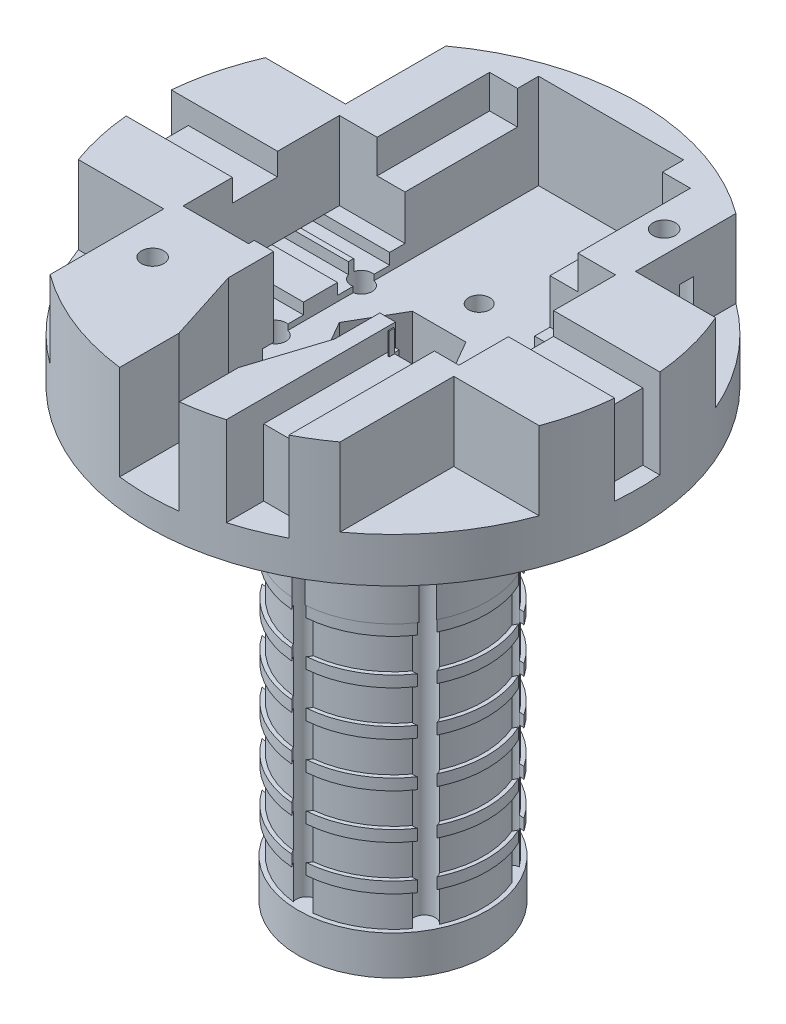
SolidWorks part; units mm, degrees
ref_plane "Front Plane" through (0, 0, 0) normal (0, 0, 1) x (1, 0, 0)
ref_plane "Top Plane" through (0, 0, 0) normal (0, 1, 0) x (1, 0, 0)
ref_plane "Right Plane" through (0, 0, 0) normal (1, 0, 0) x (0, 0, -1)
sketch "Sketch1" plane through (0, 0, 0) normal (0, 1, 0) x (1, 0, 0)
  circle A0 centre (0, 0) radius 22
extrude "Boss-Extrude1" add sketch "Sketch1" along normal blind 9 and the other way blind 2
sketch "Sketch2" plane through (0, 9, 0) normal (0, 1, 0) x (1, 0, 0)
  line L0 (0, 0) -> (0, -22) construction
  circle A0 centre (0, 0) radius 22 construction
ref_plane "Plane4" through (0, -2, 0) normal (0, -1, 0) x (-1, 0, 0)
sketch "Sketch6" plane through (0, -2, 0) normal (0, -1, 0) x (-1, 0, 0)
  circle A0 centre (0, 0) radius 21
  circle A1 centre (0, 0) radius 12.5
extrude "Cut-Extrude5" cut sketch "Sketch6" against normal blind 1
sketch "Sketch7" plane through (0, -2, 0) normal (0, -1, 0) x (-1, 0, 0)
  circle A0 centre (0, 0) radius 8.5
extrude "Boss-Extrude2" add sketch "Sketch7" along normal blind 40 contours A0
sketch "Sketch8" plane through (0, -2, 0) normal (0, -1, 0) x (-1, 0, 0)
  circle A0 centre (0, 0) radius 1.5
extrude "Cut-Extrude6" cut sketch "Sketch8" against normal through all and the other way through all contours A0
sketch "Sketch9" plane through (0, 9, 0) normal (0, 1, 0) x (1, 0, 0)
  line L0 (0, 0) -> (-13.0007, 0) construction
  line L1 (-13.0007, -20.3592) -> (-13.0007, 20.3592)
  line L2 (13, -20.3597) -> (13, 20.3597)
  line L3 (0, 0) -> (13, 0) construction
  arc A0 (13, -20.3597) -> (13, 20.3597) centre (0, 0) ccw
  arc A1 (-13.0007, 20.3592) -> (-13.0007, -20.3592) centre (0, 0) ccw
extrude "Cut-Extrude7" cut sketch "Sketch9" against normal blind 7
ref_plane "Plane5" through (0, -42, 0) normal (0, -1, 0) x (-1, 0, 0)
sketch "Sketch17" plane through (0, -42, 0) normal (0, -1, 0) x (-1, 0, 0)
  line L0 (-8.5, 0) -> (8.5, 0) construction
  line L2 (4.8118, -0.0068) -> (2.4118, 4.1501)
  line L3 (2.4118, 4.1501) -> (-2.3882, 4.1501)
  line L4 (-2.3882, 4.1501) -> (-4.7882, -0.0068)
  line L5 (-4.7882, -0.0068) -> (-2.3882, -4.1637)
  line L6 (-2.3882, -4.1637) -> (2.4118, -4.1637)
  line L7 (2.4118, -4.1637) -> (4.8118, -0.0068)
  line L38 (4.46, -2.575) -> (7.3614, -4.2497) construction
  line L39 (7.3614, -4.2497) -> (-7.3614, 4.2497) construction
  line L40 (0, 5.15) -> (0, -8.5) construction
  line L41 (0, -8.5) -> (0, 8.5) construction
  line L42 (-4.4482, -2.5818) -> (4.4718, 2.5682) construction
  line L43 (4.4718, 2.5682) -> (7.3671, 4.2398) construction
  line L44 (7.3671, 4.2398) -> (-7.3553, -4.2602) construction
  circle A0 centre (0, 0) radius 8.5 construction
  circle A1 centre (0, 0) radius 8.5 construction
  circle A2 centre (0.0118, -0.0068) radius 4.1569 construction
  circle A3 centre (-6.6912, 3.8628) radius 0.95
  circle A4 centre (-0.0004, 7.7262) radius 0.95
  circle A5 centre (6.6909, 3.8634) radius 0.95
  circle A6 centre (6.6912, -3.8628) radius 0.95
  circle A7 centre (0.0004, -7.7262) radius 0.95
  circle A9 centre (-6.6909, -3.8634) radius 0.95
  point P31 (0, 0)
extrude "Cut-Extrude14" cut sketch "Sketch17" against normal blind 62
ref_plane "Plane6" through (0, 9, 0) normal (0, 1, 0) x (1, 0, 0)
sketch "Sketch18" plane through (0, 9, 0) normal (0, 1, 0) x (1, 0, 0)
  line L0 (0, -22.0336) -> (0, 23.1421) construction
sketch "Sketch23" plane through (0, 9, 0) normal (0, 1, 0) x (1, 0, 0)
  line L0 (-2.6704, -16.8582) -> (-2.6704, -16.5304)
  line L1 (6.5, 19.5569) -> (6.5, -6.9431)
  line L2 (-6.5, 19.5569) -> (-6.5, -6.9431)
  line L3 (0, -25.25) -> (0, 0) construction
  line L4 (2.6704, -16.8582) -> (2.6704, -16.5304)
  line L5 (4.7624, -10) -> (2.5704, -16.8425) construction
  line L6 (-4.7624, -10) -> (-2.5704, -16.8425) construction
  line L7 (-4.7624, -10) -> (-2.6704, -16.5304)
  line L8 (0, -25.25) -> (-1.0006, -21.9772)
  line L9 (-6.5, 19.5569) -> (6.5, 19.5569)
  line L10 (-6.5, -6.9431) -> (-4.7624, -6.9431)
  line L11 (6.5, -6.9431) -> (4.7624, -6.9431)
  line L12 (-2.6704, -16.8582) -> (-2.6704, -21.9381) construction
  line L13 (2.6704, -16.8582) -> (2.6704, -21.9381) construction
  line L15 (1.0006, -21.9772) -> (0, -25.25)
  line L16 (4.7624, -10) -> (2.6704, -16.5304)
  line L17 (-2.6704, -16.8582) -> (-2.6704, -21.8373)
  line L19 (-4.7624, -10) -> (-4.7624, -6.9431)
  line L21 (4.7624, -10) -> (4.7624, -6.9431)
  line L22 (2.6704, -16.8582) -> (2.6704, -21.8373)
  line L32 (0, -25.592) -> (-1.0756, -22.0738) construction
  line L33 (1.0756, -22.0738) -> (0, -25.592) construction
  line L34 (4.8624, -10.0156) -> (2.6704, -16.8582) construction
  line L35 (4.8624, -10.0156) -> (4.8624, -7.0431) construction
  line L36 (6.6, -7.0431) -> (4.8624, -7.0431) construction
  line L37 (6.6, 19.6569) -> (6.6, -7.0431) construction
  line L38 (-6.6, 19.6569) -> (6.6, 19.6569) construction
  line L39 (-6.6, 19.6569) -> (-6.6, -7.0431) construction
  line L40 (-6.6, -7.0431) -> (-4.8624, -7.0431) construction
  line L41 (-4.8624, -10.0156) -> (-4.8624, -7.0431) construction
  line L42 (-4.8624, -10.0156) -> (-2.6704, -16.8582) construction
  line L43 (2.5704, -16.8425) -> (2.5704, -21.8493) construction
  line L44 (-2.5704, -16.8425) -> (-2.5704, -21.8493) construction
  arc A0 (-2.6704, -21.8373) -> (-1.0006, -21.9772) centre (0, 0) ccw
  arc A1 (1.0006, -21.9772) -> (2.6704, -21.8373) centre (0, 0) ccw
  arc A4 (1.0756, -22.0738) -> (2.6704, -21.9381) centre (0, 0) ccw construction
  arc A5 (-2.6704, -21.9381) -> (-1.0756, -22.0738) centre (0, 0) ccw construction
  arc A6 (-2.5704, -21.8493) -> (-1.0006, -21.9772) centre (0, 0) ccw construction
  arc A7 (1.0006, -21.9772) -> (2.5704, -21.8493) centre (0, 0) ccw construction
  dimension "D1" = 180
ref_plane "Plane10" through (0, 0, 6.4558) normal (0, 0, -1) x (-1, 0, 0)
sketch "Sketch29" plane through (0, 9, 0) normal (0, 1, 0) x (1, 0, 0)
  line L0 (9, 17.6622) -> (9, -6.4558)
  line L1 (9, 17.6622) -> (-9, 17.6622)
  line L2 (9, -6.4558) -> (-9, -6.4558)
  line L3 (0, -6.4558) -> (0, 17.6622) construction
  line L4 (-9, -6.4558) -> (-9, 17.6622)
  point P5 (0, -6.4558)
  point P8 (0, 17.6622)
extrude "Cut-Extrude19" cut sketch "Sketch29" against normal blind 3
sketch "Sketch30" plane through (0, 9, 0) normal (0, 1, 0) x (1, 0, 0)
  line L0 (-8.0021, 17.6622) -> (-8.0021, -6.4558) construction
  line L1 (8.0021, -6.4558) -> (5.5021, -6.4558)
  line L2 (8.0021, -6.4558) -> (8.0021, 7.5442)
  line L3 (8.0021, 7.5442) -> (5.5021, 7.5442)
  line L4 (-8.0021, -6.4558) -> (-8.0021, 7.5442)
  line L5 (5.5021, 7.5442) -> (5.5021, -6.4558)
  line L8 (-5.5021, 7.5442) -> (-5.5021, -6.4558)
  line L9 (-5.5021, 7.5442) -> (-8.0021, 7.5442)
  line L10 (-5.5021, -6.4558) -> (-8.0021, -6.4558)
  point P7 (5.5021, 7.5442)
  dimension "D1" = 2.5
extrude "Cut-Extrude20" cut sketch "Sketch30" against normal blind 6
ref_plane "Plane11" through (0, 3, 0) normal (0, -1, 0) x (-1, 0, 0)
sketch "Sketch32" plane through (0, 3, 0) normal (0, -1, 0) x (-1, 0, 0)
  circle A1 centre (-5.1962, -3) radius 0.85
  circle A3 centre (5.1962, -3) radius 0.85
  circle A5 centre (5.1962, 3) radius 0.85
  circle A6 centre (-5.1962, 3) radius 0.85
  circle A7 centre (0, 6) radius 0.0479
  circle A8 centre (0, 6) radius 0.85
  circle A9 centre (0, -6) radius 0.85
extrude "Cut-Extrude22" [suppressed] cut sketch "Sketch32" against normal blind 11 and the other way through all
ref_plane "Plane12" through (0, 2, 0) normal (0, 1, 0) x (1, 0, 0)
sketch "Sketch33" [suppressed] plane through (0, 2, 0) normal (0, 1, 0) x (1, 0, 0)
  circle A0 centre (5.1962, 3) radius 1.1
  circle A1 centre (5.1962, -3) radius 1.1
  circle A2 centre (-5.1962, 3) radius 1.1
  circle A3 centre (-5.1962, -3) radius 1.1
  circle A4 centre (0, -6) radius 1.1
  circle A5 centre (0, 6) radius 1.1
extrude "Cut-Extrude23" [suppressed] cut sketch "Sketch33" against normal blind 2 and the other way through all
ref_plane "Plane13" through (0, 2, 0) normal (0, 1, 0) x (1, 0, 0)
sketch "Sketch34" plane through (0, 2, 0) normal (0, 1, 0) x (1, 0, 0)
  line L0 (-1.3341, 5.3583) -> (7.9939, 5.3583)
  line L1 (-7.985, 6.6083) -> (-1.2507, 6.6083)
  line L2 (-7.985, 6.6083) -> (-7.985, 5.3583)
  line L3 (-7.985, 5.3583) -> (-1.3341, 5.3583)
  line L4 (7.9939, 6.6083) -> (7.9939, 5.3583)
  line L5 (-1.2507, 6.6083) -> (7.9939, 6.6083)
  line L6 (8.0021, -6.4558) -> (-8.0021, -6.4558)
  line L7 (-8.0021, -6.4558) -> (-8.0021, -5.2058)
  line L8 (-8.0021, 7.5442) -> (-8.0021, -6.4558) construction
  line L9 (-8.0021, -5.2058) -> (8.0021, -5.2058)
  line L10 (8.0021, -5.2058) -> (8.0021, -6.4558)
extrude "Cut-Extrude27" [suppressed] cut sketch "Sketch34" against normal blind 2
ref_plane "Plane14" through (0, -6.5, 0) normal (0, 1, 0) x (1, 0, 0)
sketch "Sketch35" plane through (0, -6.5, 0) normal (0, 1, 0) x (1, 0, 0)
  circle A0 centre (0, 0) radius 8.5
  circle A1 centre (0, 0) radius 9.1
extrude "Boss-Extrude4" add sketch "Sketch35" along normal blind 2 and the other way blind 2
ref_plane "Plane15" through (0, -17, 0) normal (0, 1, 0) x (1, 0, 0)
sketch "Sketch36" plane through (0, -17, 0) normal (0, 1, 0) x (1, 0, 0)
  line L1 (55, -6.4558) -> (-55, -6.4558) construction
  circle A0 centre (0, 0) radius 8.1
  circle A1 centre (0, 0) radius 8.5
extrude "Cut-Extrude28" cut sketch "Sketch36" against normal blind 1.5 and the other way blind 1.5
ref_plane "Plane16" through (0, -21, 0) normal (0, 1, 0) x (1, 0, 0)
ref_plane "Plane17" through (0, -25, 0) normal (0, 1, 0) x (1, 0, 0)
ref_plane "Plane18" through (0, -29, 0) normal (0, 1, 0) x (1, 0, 0)
ref_plane "Plane19" through (0, -33, 0) normal (0, 1, 0) x (1, 0, 0)
ref_plane "Plane20" through (0, -37, 0) normal (0, 1, 0) x (1, 0, 0)
sketch "Sketch39" plane through (0, -21, 0) normal (0, 1, 0) x (1, 0, 0)
  circle A0 centre (0, 0) radius 8.1
  circle A1 centre (0, 0) radius 8.5
extrude "Cut-Extrude30" cut sketch "Sketch39" against normal blind 1.5 and the other way blind 1.5
sketch "Sketch40" plane through (0, -25, 0) normal (0, 1, 0) x (1, 0, 0)
  circle A0 centre (0, 0) radius 8.1
  circle A1 centre (0, 0) radius 8.5
extrude "Cut-Extrude31" cut sketch "Sketch40" against normal blind 1.5 and the other way blind 1.5
sketch "Sketch41" plane through (0, -29, 0) normal (0, 1, 0) x (1, 0, 0)
  circle A0 centre (0, 0) radius 8.1
  circle A1 centre (0, 0) radius 8.5
extrude "Cut-Extrude32" cut sketch "Sketch41" against normal blind 1.5 and the other way blind 1.5
sketch "Sketch42" plane through (0, -33, 0) normal (0, 1, 0) x (1, 0, 0)
  circle A0 centre (0, 0) radius 8.1
  circle A1 centre (0, 0) radius 8.5
extrude "Cut-Extrude33" cut sketch "Sketch42" against normal blind 1.5 and the other way blind 1.5
sketch "Sketch43" plane through (0, -37, 0) normal (0, 1, 0) x (1, 0, 0)
  circle A0 centre (0, 0) radius 8.1
  circle A1 centre (0, 0) radius 8.5
extrude "Cut-Extrude34" cut sketch "Sketch43" against normal blind 1.5 and the other way blind 1.5
sketch "Sketch44" plane through (0, 0, 0) normal (0, 0, 1) x (1, 0, 0)
  line L0 (0, 0) -> (0, -16.9756) construction
  line L1 (0, -16.9756) -> (0, -29.0422) construction
  circle A0 centre (0, -16.9756) radius 1
  circle A1 centre (0, -29.0422) radius 1
extrude "Cut-Extrude35" [suppressed] cut sketch "Sketch44" against normal through all and the other way through all
ref_axis "Axis1" through (0, -42, 0) along (0, 1, 0)
ref_plane "Plane21" through (0, 0, 0) normal (0.866, 0, 0.5) x (0, 1, 0)
sketch "Sketch45" plane through (0, 0, 0) normal (0.866, 0, 0.5) x (0, 1, 0)
  line L0 (0, 0) -> (-21.1015, 0) construction
  line L1 (-21.1015, 0) -> (-33.0495, 0) construction
  circle A0 centre (-21.1015, 0) radius 1
  circle A1 centre (-33.0495, 0) radius 1
extrude "Cut-Extrude36" [suppressed] cut sketch "Sketch45" against normal through all and the other way through all
ref_plane "Plane22" through (0, 0, 0) normal (0.866, 0, -0.5) x (0, 1, 0)
sketch "Sketch46" plane through (0, 0, 0) normal (0.866, 0, -0.5) x (0, 1, 0)
  line L0 (0, 0) -> (-24.961, 0) construction
  line L1 (-24.961, 0) -> (-37.1304, 0) construction
  circle A0 centre (-24.961, 0) radius 1
  circle A1 centre (-37.1304, 0) radius 1
extrude "Cut-Extrude37" [suppressed] cut sketch "Sketch46" against normal through all and the other way through all
ref_plane "Plane23" through (0, 9, 0) normal (0, 1, 0) x (1, 0, 0)
sketch "Sketch47" plane through (0, 9, 0) normal (0, 1, 0) x (1, 0, 0)
  line L1 (13.8544, -6.4558) -> (-13.8777, -6.4558)
  line L2 (13.8544, -6.4558) -> (13.8544, 7.5778)
  line L3 (13.8544, 7.5778) -> (-13.8777, 7.5778)
  line L4 (-13.8777, -6.4558) -> (-13.8777, 7.5778)
extrude "Cut-Extrude38" cut sketch "Sketch47" against normal blind 7
extrude "Cut-Extrude39" cut sketch "Sketch23" against normal blind 8.5
sketch "Sketch48" plane through (0, 9, 0) normal (0, 1, 0) x (1, 0, 0)
  line L0 (0, 0) -> (0, 34.87) construction
  line L1 (11, 7.5778) -> (11, 19.0526) construction
  line L2 (13, 7.5778) -> (9, 7.5778) construction
  line L3 (11, 19.0526) -> (11, 13.3152) construction
  line L4 (11, 13.3152) -> (0, 0) construction
  line L5 (0, 0) -> (-17.1456, -20.7543) construction
  line L6 (-9.7504, -6.4558) -> (-9.7504, -16.5924) construction
  line L7 (-13.0007, -6.4558) -> (-6.5, -6.4558) construction
  arc A0 (13, 17.7482) -> (-13.0007, 17.7477) centre (0, 0) ccw construction
  circle A1 centre (11, 13.3152) radius 1
  circle A2 centre (-9.7504, -11.8025) radius 1
  dimension "D1" = 39.561
extrude "Cut-Extrude40" cut sketch "Sketch48" against normal blind 9
sketch "Sketch49" plane through (0, -1, 0) normal (0, -1, 0) x (1, 0, 0)
  circle A0 centre (-9.7504, 11.8025) radius 2.1
  circle A1 centre (11, -13.3152) radius 2.1
sketch "Sketch50" plane through (0, -42, 0) normal (0, -1, 0) x (1, 0, 0)
  line L0 (4.9897, 0.0006) -> (-4.9897, -0.0006) construction
  line L2 (-4.9897, -0.0006) -> (-2.4943, -4.3215)
  line L3 (-2.4943, -4.3215) -> (2.4953, -4.3209)
  line L4 (2.4953, -4.3209) -> (4.9897, 0.0006)
  line L5 (4.9897, 0.0006) -> (2.4943, 4.3215)
  line L6 (2.4943, 4.3215) -> (-2.4953, 4.3209)
  line L7 (-2.4953, 4.3209) -> (-4.9897, -0.0006)
  circle A0 centre (0, 0) radius 4.3212 construction
  circle A1 centre (0, 0) radius 6.3883
extrude "Boss-Extrude5" add sketch "Sketch50" against normal blind 2
sketch "Sketch51" plane through (0, 2, 0) normal (0, 1, 0) x (1, 0, 0)
  line L0 (1.1188, 6.2) -> (17.8187, 6.2)
  line L1 (-4.46, 2.575) -> (4.46, 2.575) construction
  line L2 (-1.1188, 10.9848) -> (1.1188, 10.9848)
  line L3 (-17.8187, 4.1) -> (-1.1188, 4.1)
  line L4 (-17.8187, 4.1) -> (-17.8187, 6.2)
  line L5 (-17.8187, 6.2) -> (-1.1188, 6.2)
  line L6 (17.8187, 4.1) -> (17.8187, 6.2)
  line L7 (-17.8187, 4.1) -> (17.8187, 6.2) construction
  line L8 (-17.8187, 6.2) -> (17.8187, 4.1) construction
  line L9 (-4.46, -2.575) -> (4.46, -2.575) construction
  line L10 (-17.8187, 3.625) -> (-1.1188, 3.625)
  line L11 (-17.8187, 3.625) -> (-17.8187, 1.525)
  line L12 (-17.8187, 1.525) -> (-1.1188, 1.525)
  line L13 (17.8187, 3.625) -> (17.8187, 1.525)
  line L14 (-17.8187, 3.625) -> (17.8187, 1.525) construction
  line L15 (-17.8187, 1.525) -> (17.8187, 3.625) construction
  line L16 (-1.1188, 10.9848) -> (-1.1188, 6.2)
  line L17 (-17.8187, -3.625) -> (-1.1188, -3.625)
  line L18 (-17.8187, -3.625) -> (-17.8187, -1.525)
  line L19 (-17.8187, -1.525) -> (-1.1188, -1.525)
  line L20 (17.8187, -3.625) -> (17.8187, -1.525)
  line L21 (-17.8187, -3.625) -> (17.8187, -1.525) construction
  line L22 (-17.8187, -1.525) -> (17.8187, -3.625) construction
  line L23 (-17.8187, -6.2) -> (-1.1188, -6.2)
  line L24 (-17.8187, -6.2) -> (-17.8187, -4.1)
  line L25 (-17.8187, -4.1) -> (-1.1188, -4.1)
  line L26 (17.8187, -6.2) -> (17.8187, -4.1)
  line L27 (-17.8187, -6.2) -> (17.8187, -4.1) construction
  line L28 (-17.8187, -4.1) -> (17.8187, -6.2) construction
  line L29 (-1.1188, -10.9848) -> (1.1188, -10.9848)
  line L30 (1.1188, 10.9848) -> (1.1188, 6.2)
  line L31 (-1.1188, 10.9848) -> (1.1188, -10.9848) construction
  line L32 (-1.1188, -10.9848) -> (1.1188, 10.9848) construction
  line L33 (1.1188, 4.1) -> (1.1188, 3.625)
  line L34 (-1.1188, 4.1) -> (-1.1188, 3.625)
  line L35 (1.1188, 4.1) -> (17.8187, 4.1)
  line L36 (1.1188, 3.625) -> (17.8187, 3.625)
  line L37 (1.1188, 1.525) -> (17.8187, 1.525)
  line L38 (-1.1188, 1.525) -> (-1.1188, -1.525)
  line L39 (1.1188, -1.525) -> (17.8187, -1.525)
  line L40 (1.1188, 1.525) -> (1.1188, -1.525)
  line L41 (1.1188, -3.625) -> (17.8187, -3.625)
  line L42 (1.1188, -4.1) -> (17.8187, -4.1)
  line L43 (1.1188, -3.625) -> (1.1188, -4.1)
  line L44 (-1.1188, -3.625) -> (-1.1188, -4.1)
  line L46 (-1.1188, -6.2) -> (-1.1188, -10.9848)
  line L47 (1.1188, -6.2) -> (17.8187, -6.2)
  line L48 (1.1188, -6.2) -> (1.1188, -10.9848)
  point P0 (0, 5.15)
  point P7 (0, 2.575)
  point P14 (0, -2.575)
  point P15 (0, 0)
  point P22 (0, -5.15)
extrude "Cut-Extrude42" cut sketch "Sketch49" against normal blind 7
extrude "Cut-Extrude43" cut sketch "Sketch51" against normal blind 1
sketch "Sketch52" plane through (0, 9, 0) normal (0, 1, 0) x (1, 0, 0)
  line L0 (4.7624, -6.9431) -> (4.7624, -20.5361) construction
  line L1 (4.7624, -17.7644) -> (8.1673, -17.7644) construction
  line L2 (6.1673, -17.7644) -> (10.1673, -17.7644)
  line L3 (6.1673, -17.7644) -> (6.1673, -6.9431)
  line L4 (4.7624, -6.9431) -> (6.6, -6.9431) construction
  line L5 (10.1673, -17.7644) -> (10.1673, -6.4558)
  line L6 (55, -6.4558) -> (-55, -6.4558) construction
  line L7 (10.1673, -6.4558) -> (6.6, -6.4558)
  line L8 (6.6, -6.4558) -> (6.6, -6.2) construction
  line L9 (6.6, -6.4558) -> (6.6, -6.9431)
  line L10 (6.6, -6.9431) -> (6.1673, -6.9431)
  point P8 (8.1673, -17.7644)
extrude "Cut-Extrude44" cut sketch "Sketch52" against normal blind 2
sketch "Sketch53" plane through (0, -42, 0) normal (0, -1, 0) x (1, 0, 0)
  circle A0 centre (0, 0) radius 8.5
  circle A1 centre (0, 0) radius 8.45
extrude "Cut-Extrude45" cut sketch "Sketch53" against normal blind 27.5
sketch "Sketch54" plane through (0, 9, 0) normal (0, 1, 0) x (1, 0, 0)
  line L0 (10.1673, -17.7644) -> (10.1673, -19.5096)
  line L1 (6.1673, -17.7644) -> (6.1673, -21.1179)
  line L2 (6.1673, -21.1179) -> (6.1673, -17.7644)
  arc A0 (6.1673, -21.1179) -> (10.1673, -19.5096) centre (0, 0) ccw
  line M2 (10.1673, -17.7644) -> (6.1673, -17.7644)
  arc M8 (2.6704, -21.8373) -> (13, -17.7482) centre (0, 0) ccw
extrude "Cut-Extrude46" cut sketch "Sketch54" against normal blind 8 contours L1 L0 M2 M8 region at (7.9636, 9, 19.1182)
sketch "Sketch55" plane through (0, 0, 6.9431) normal (0, 0, -1) x (-1, 0, 0)
  line L0 (-4.7624, 9) -> (-6.1673, 9)
  line L1 (-6.1673, 9) -> (-6.1673, 7)
  line L2 (-6.1673, 7) -> (-6.5, 7)
  line L3 (-6.5, 7) -> (-6.5, 1.9457)
  line L4 (-6.5, 1.9457) -> (-4.7624, 1.9457)
  line L5 (-4.7624, 1.9457) -> (-4.7624, 9)
  line L6 (6.5, 9) -> (4.7624, 9)
  line L7 (4.7624, 9) -> (4.7624, 1.9457)
  line L8 (4.7624, 0.5) -> (4.7624, 9) construction
  line L9 (4.7624, 1.9457) -> (6.5, 1.9457)
  line L10 (6.5, 0.5) -> (6.5, 9) construction
  line L11 (6.5, 1.9457) -> (6.5, 9)
extrude "Boss-Extrude6" add sketch "Sketch55" along normal blind 1
sketch "Sketch56" plane through (0, 2, 0) normal (0, 1, 0) x (1, 0, 0)
  line L0 (12.3665, -7.5517) -> (12.3838, 8.7422)
  line L1 (12.3665, -7.5517) -> (20.6633, -7.5517)
  line L3 (12.3838, 8.7422) -> (20.1885, 8.7422)
  arc A0 (20.6633, -7.5517) -> (20.1885, 8.7422) centre (0, 0) ccw
extrude "Boss-Extrude12" add sketch "Sketch56" along normal blind 7
sketch "Sketch57" plane through (0, 9, 0) normal (0, 1, 0) x (1, 0, 0)
  line L0 (0, 0) -> (22, 0) construction
  line L1 (11.943, -2.0251) -> (11.943, 2.0251)
  line L3 (11.943, 2.0251) -> (22.3347, 2.0251)
  line L4 (22.3347, 2.0251) -> (22.3347, -2.0251)
  line L5 (22.3347, -2.0251) -> (11.943, -2.0251)
  arc A0 (20.6633, -7.5517) -> (20.1885, 8.7422) centre (0, 0) ccw construction
  point P10 (11.943, 0)
extrude "Cut-Extrude49" cut sketch "Sketch57" against normal blind 2
sketch "Sketch58" plane through (0, 9, 0) normal (0, 1, 0) x (1, 0, 0)
  line L0 (21.9066, -2.0251) -> (20.3765, -2.0251)
  line L1 (12.3723, -2.0251) -> (21.9066, -2.0251) construction
  line L2 (20.3765, -2.0251) -> (20.3765, 2.0251)
  line L3 (21.9066, 2.0251) -> (12.3766, 2.0251) construction
  line L4 (20.3765, 2.0251) -> (21.9066, 2.0251)
  arc A0 (21.9066, -2.0251) -> (21.9066, 2.0251) centre (0, 0) ccw
extrude "Cut-Extrude50" cut sketch "Sketch58" against normal blind 8
mirror "Mirror1" about plane through (0, 0, 0) normal (1, 0, 0) of "Boss-Extrude12"
mirror "Mirror2" about plane through (0, 0, 0) normal (1, 0, 0) of "Cut-Extrude50", "Cut-Extrude49"
sketch "Sketch59" plane through (0, -42, 0) normal (0, -1, 0) x (-1, 0, 0)
  circle A0 centre (0, 0) radius 8.5
  circle A1 centre (0, 0) radius 4.9551
extrude "Boss-Extrude13" add sketch "Sketch59" against normal blind 3.5
